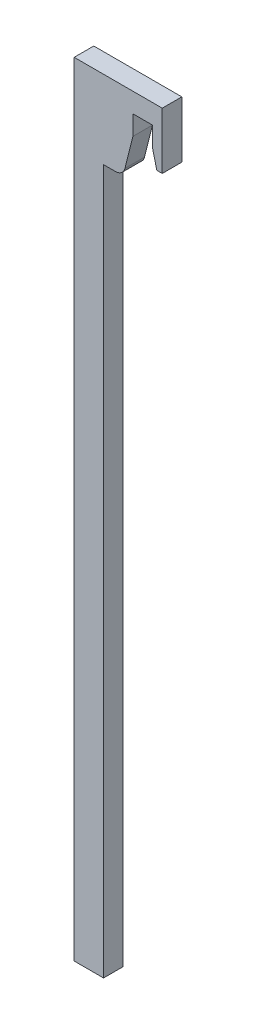
SolidWorks part; units mm, degrees
ref_plane "Front Plane" through (0, 0, 0) normal (0, 0, 1) x (1, 0, 0)
ref_plane "Top Plane" through (0, 0, 0) normal (0, 1, 0) x (1, 0, 0)
ref_plane "Right Plane" through (0, 0, 0) normal (1, 0, 0) x (0, 0, -1)
sketch "Sketch1" plane through (0, 0, 0) normal (0, 0, 1) x (1, 0, 0)
  line L13 (-5, 10) -> (5, 10)
  line L18 (10, 20) -> (-10, 20)
  line L19 (10, 20) -> (10, -20)
  line L25 (-10, 20) -> (-10, -20)
  line L26 (10, 20) -> (-10, -20) construction
  line L27 (10, -20) -> (-10, 20) construction
  line L28 (-5, 10) -> (-5, 0)
  line L29 (5, 10) -> (5, 0)
  line L30 (-5, 0) -> (-10, -20)
  line L31 (5, 0) -> (10, -20)
  line L32 (-10, 20) -> (-35, 20)
  line L33 (-35, 20) -> (-35, -380)
  line L34 (-35, -380) -> (-20, -380)
  line L35 (-20, -380) -> (-20, 0)
  line L36 (-20, 0) -> (-10, 0)
  line L37 (-10, -20) -> (-20, -20)
  line L38 (10, 20) -> (15, 20)
  line L39 (15, 20) -> (15, -20)
  line L40 (15, -20) -> (10, -20)
  point P0 (0, 0)
  point P1 (0, 0)
  point P5 (0, 0)
  point P7 (0, 20)
  point P12 (0, 10)
  point P15 (-10, 0)
  dimension "D1" = 20
  dimension "D2" = 10
  dimension "D3" = 10
  dimension "D4" = 10
  dimension "D5" = 10
  dimension "D6" = 40
  dimension "D7" = 25
  dimension "D8" = 15
  dimension "D9" = 400
  dimension "D10" = 5
extrude "Boss-Extrude2" add sketch "Sketch1" along normal mid plane 10 contours L29 L31 L19 L18 L25 L30 L28 L13 | L35 L36 L25 L32 L33 L34 | L37 L25 L36 L35 region at (-5.4472, 5, 0) region at (-15, -10, 0) region at (-27.0968, -173.871, 0)
fillet "Fillet2" radius 5 1 edges at (-10, -20, 0)
sketch "Sketch2" plane through (0, 0, -5) normal (0, 0, -1) x (-1, 0, 0)
  line L0 (-10, -8.9255) -> (-7.2314, -8.9255)
  line L1 (-10, 20) -> (-10, -20) construction
  line L2 (-5, 0) -> (-10, -20) construction
  line L3 (-7.2314, -8.9255) -> (-10, -20)
  line L4 (-10, -8.9255) -> (-10, -20)
  dimension "D1" = 2.7686
extrude "Cut-Extrude2" cut sketch "Sketch2" against normal blind 10
